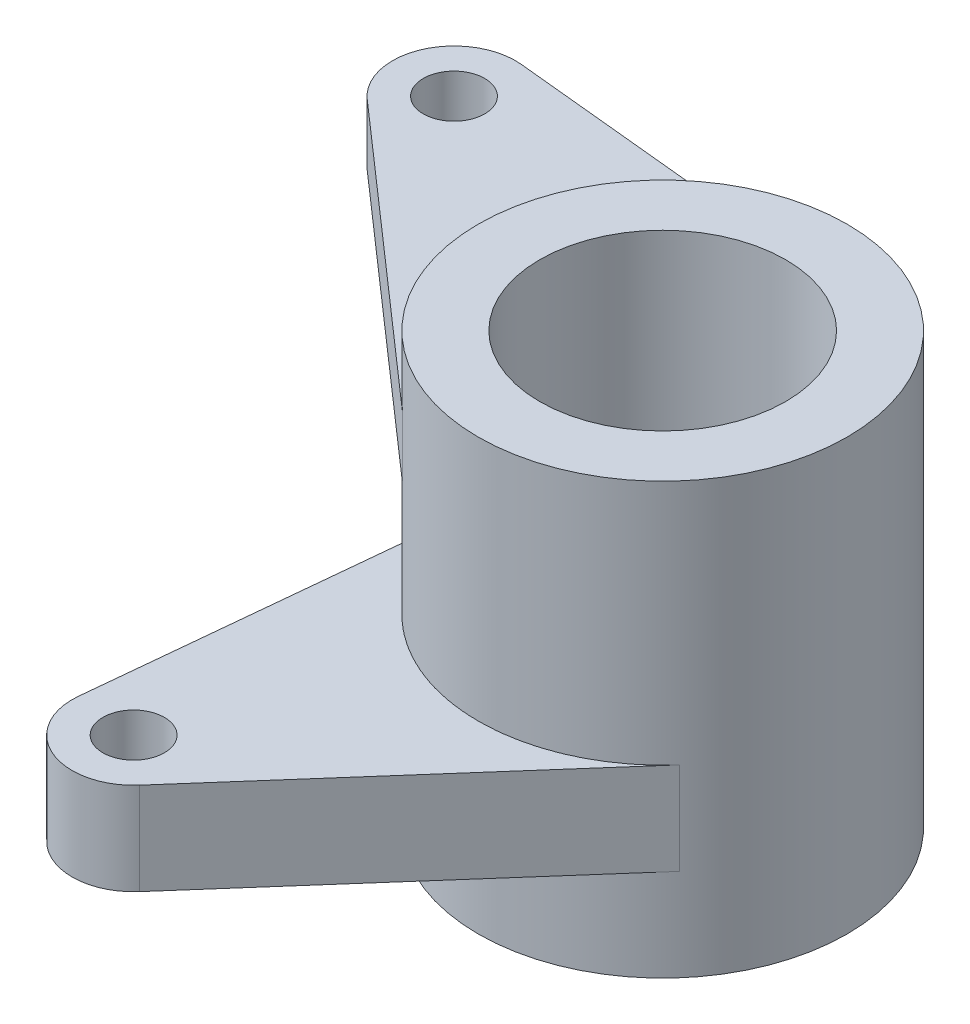
SolidWorks part; units mm, degrees
ref_plane "Front Plane" through (0, 0, 0) normal (0, 0, 1) x (1, 0, 0)
ref_plane "Top Plane" through (0, 0, 0) normal (0, 1, 0) x (1, 0, 0)
ref_plane "Right Plane" through (0, 0, 0) normal (1, 0, 0) x (0, 0, -1)
sketch "Sketch1" plane through (0, 0, 0) normal (0, 1, 0) x (1, 0, 0)
  circle A0 centre (0, 0) radius 30
  circle A1 centre (0, 0) radius 20
  dimension "D1" = 60
  dimension "D2" = 40
extrude "Boss-Extrude1" add sketch "Sketch1" against normal blind 70
sketch "Sketch2" plane through (0, 0, 0) normal (0, 1, 0) x (1, 0, 0)
  line L0 (2.9644, 29.8532) -> (-59.0119, 36.0074)
  line L1 (-66.597, 18.5411) -> (-19.791, -22.5458)
  circle A1 centre (0, 0) radius 30 construction
  arc A2 (-59.0119, 36.0074) -> (-66.597, 18.5411) centre (-60, 26.0564) ccw
  arc A3 (2.9644, 29.8532) -> (-19.791, -22.5458) centre (0, 0) ccw
  circle A4 centre (-60, 26.0564) radius 5
  dimension "D2" = 10
  dimension "D3" = 10
  dimension "D1" = 60
extrude "Boss-Extrude2" add sketch "Sketch2" against normal blind 10 from offset 10 offset against normal yes
extrude "Boss-Extrude3" add sketch "Sketch2<3>" against normal blind 15 from offset 40 separate body offset against normal yes
sketch "Sketch2<3>" plane through (0, 0, 0) normal (0, 1, 0) x (1, 0, 0) same geometry as "Sketch2"
ref_axis "Axis1" through (0, -70, 0) along (0, 1, 0)
move or copy body "Body-Move/Copy1" bodies to move or copy 103 copy no rotation origin (0, 0, 0) rotation axis (0, 1, 0) rotation angle 90
